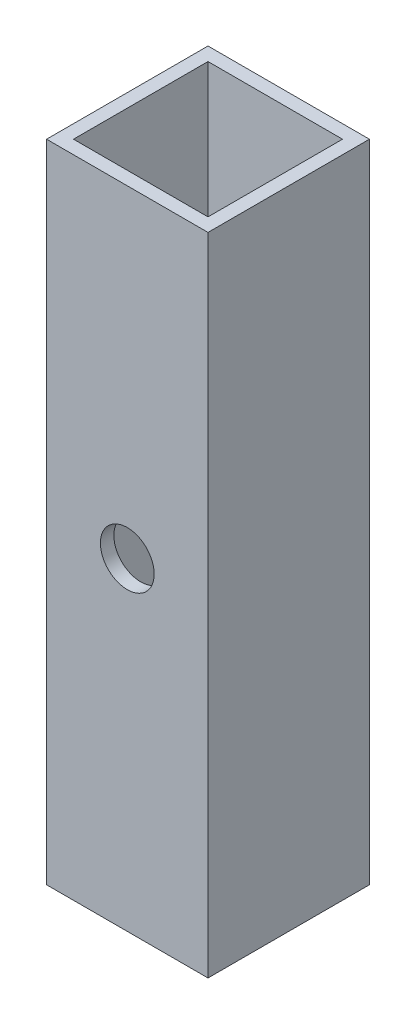
SolidWorks part; units mm, degrees
material "Plain Carbon Steel"
ref_plane "Front Plane" through (0, 0, 0) normal (0, 0, 1) x (1, 0, 0)
ref_plane "Top Plane" through (0, 0, 0) normal (0, 1, 0) x (1, 0, 0)
ref_plane "Right Plane" through (0, 0, 0) normal (1, 0, 0) x (0, 0, -1)
sketch "Sketch1" plane through (0, 0, 0) normal (0, 1, 0) x (1, 0, 0)
  line L0 (0, 19.05) -> (3.175, 19.05) construction
  line L1 (0, 0) -> (38.1, 0)
  line L2 (0, 0) -> (0, 38.1)
  line L3 (0, 38.1) -> (38.1, 38.1)
  line L4 (38.1, 0) -> (38.1, 38.1)
  line L5 (3.175, 3.175) -> (34.925, 3.175)
  line L6 (3.175, 3.175) -> (3.175, 34.925)
  line L7 (3.175, 34.925) -> (34.925, 34.925)
  line L8 (34.925, 3.175) -> (34.925, 34.925)
  line L9 (34.925, 19.05) -> (38.1, 19.05) construction
  line L10 (19.05, 3.175) -> (19.05, 0) construction
  line L11 (19.05, 34.925) -> (19.05, 38.1) construction
  dimension "D1" = 38.1
  dimension "D2" = 38.1
  dimension "D3" = 3.175
extrude "Boss-Extrude1" add sketch "Sketch1" along normal blind 152.4
hole_wizard "1/2 (0.5) Diameter Hole1" positions "Sketch3" profile "Sketch2" hole size "1/2" standard "ANSI Inch" end condition through all
sketch "Sketch3" plane through (0, 0, 0) normal (0, 0, 1) x (1, 0, 0)
  line L0 (19.05, 0) -> (19.05, 76.2) construction
  line L1 (0, 0) -> (38.1, 0) construction
  line L2 (19.05, 76.2) -> (19.05, 152.4) construction
  line L3 (0, 152.4) -> (38.1, 152.4) construction
  point P0 (19.05, 76.2)
sketch "Sketch2" plane through (19.05, 76.2, 0) normal (1, 0, 0) x (0, -1, 0)
  line L0 (0, 0) -> (0, 38.1)
  line L1 (0, 38.1) -> (6.35, 38.1)
  line L2 (6.35, 38.1) -> (6.35, 0)
  line L5 (6.35, 0) -> (0, 0)
  line L11 (0, -6.35) -> (0, 107.95) construction
  dimension "Thru Hole Dia." = 12.7
  dimension "Thru Hole Depth" = 38.1
